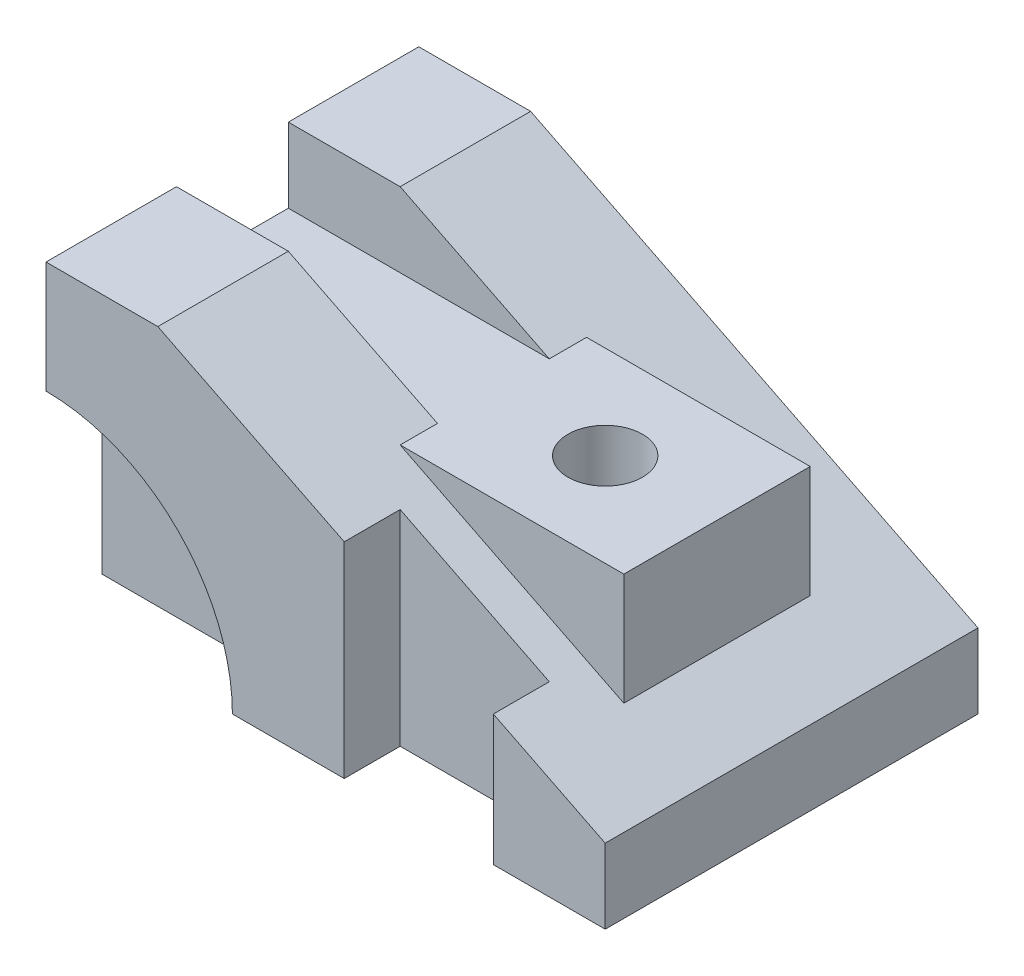
SolidWorks part; units mm, degrees
ref_plane "Front Plane" through (0, 0, 0) normal (0, 0, 1) x (1, 0, 0)
ref_plane "Top Plane" through (0, 0, 0) normal (0, 1, 0) x (1, 0, 0)
ref_plane "Right Plane" through (0, 0, 0) normal (1, 0, 0) x (0, 0, -1)
sketch "Sketch1" plane through (0, 0, 0) normal (0, 0, 1) x (1, 0, 0)
  line L0 (0, 0) -> (150, 0)
  line L1 (150, 0) -> (150, 20)
  line L2 (150, 20) -> (30, 80)
  line L3 (30, 80) -> (0, 80)
  line L4 (0, 80) -> (0, 0)
  dimension "D1" = 20
  dimension "D2" = 150
  dimension "D3" = 80
  dimension "D4" = 30
extrude "Boss-Extrude1" add sketch "Sketch1" against normal blind 50 and the other way blind 50
sketch "Sketch3" plane through (0, 0, 50) normal (0, 0, 1) x (1, 0, 0)
  circle A0 centre (0, 0) radius 50
  dimension "D1" = 100
extrude "Cut-Extrude1" cut sketch "Sketch3" against normal blind 15
sketch "Sketch4" plane through (0, 0, 0) normal (0, 0, 1) x (1, 0, 0)
  line L0 (70, 60) -> (130, 60)
  line L1 (150, 20) -> (30, 80) construction
  line L2 (130, 60) -> (130, 30)
  line L3 (150, 0) -> (150, 20) construction
  line L4 (150, 20) -> (130, 30)
  line L9 (50, 0) -> (150, 0)
  line L10 (150, 0) -> (150, 20)
  line L11 (150, 20) -> (30, 80)
  line L12 (30, 80) -> (0, 80)
  line L13 (0, 80) -> (0, 50)
  line L14 (50, 0) -> (150, 0)
  line L15 (150, 0) -> (150, 20)
  line L16 (70, 60) -> (30, 80)
  line L17 (30, 80) -> (0, 80)
  line L18 (0, 80) -> (0, 50)
  arc A1 (50, 0) -> (0, 50) centre (0, 0) ccw
  arc A2 (50, 0) -> (0, 50) centre (0, 0) ccw
  dimension "D1" = 20
  dimension "D2" = 30
  dimension "D3" = 0
extrude "Boss-Extrude2" add sketch "Sketch4" along normal blind 25 and the other way blind 25 contours L0 L2 L4 L15 L14 A2 L18 L17 L16
sketch "Sketch5" plane through (0, 60, 0) normal (0, 1, 0) x (1, 0, 0)
  line L0 (30, 50) -> (0, 50) construction
  line L1 (-42.84, 15) -> (117.7252, 15)
  line L2 (-42.84, 15) -> (-42.84, -15)
  line L3 (-42.84, -15) -> (117.7252, -15)
  line L4 (117.7252, 15) -> (117.7252, -15)
  line L5 (30, -50) -> (0, -50) construction
  dimension "D1" = 35
  dimension "D2" = 35
extrude "Cut-Extrude2" cut sketch "Sketch5" along normal through all
sketch "Sketch6" plane through (0, 60, 0) normal (0, 1, 0) x (1, 0, 0)
  line L0 (130, 25) -> (130, -25) construction
  circle A0 centre (100, 0) radius 10
  dimension "D2" = 20
  dimension "D1" = 30
extrude "Cut-Extrude3" cut sketch "Sketch6" against normal through all
sketch "Sketch7" plane through (0, 0, 0) normal (0, -1, 0) x (1, 0, 0)
  line L0 (50, 50) -> (150, 50) construction
  line L1 (80, 50) -> (120, 50)
  line L2 (80, 50) -> (80, 35)
  line L3 (80, 35) -> (120, 35)
  line L4 (120, 50) -> (120, 35)
  line L5 (150, 50) -> (150, -50) construction
  dimension "D1" = 30
  dimension "D2" = 15
  dimension "D3" = 40
extrude "Cut-Extrude4" cut sketch "Sketch7" against normal through all
